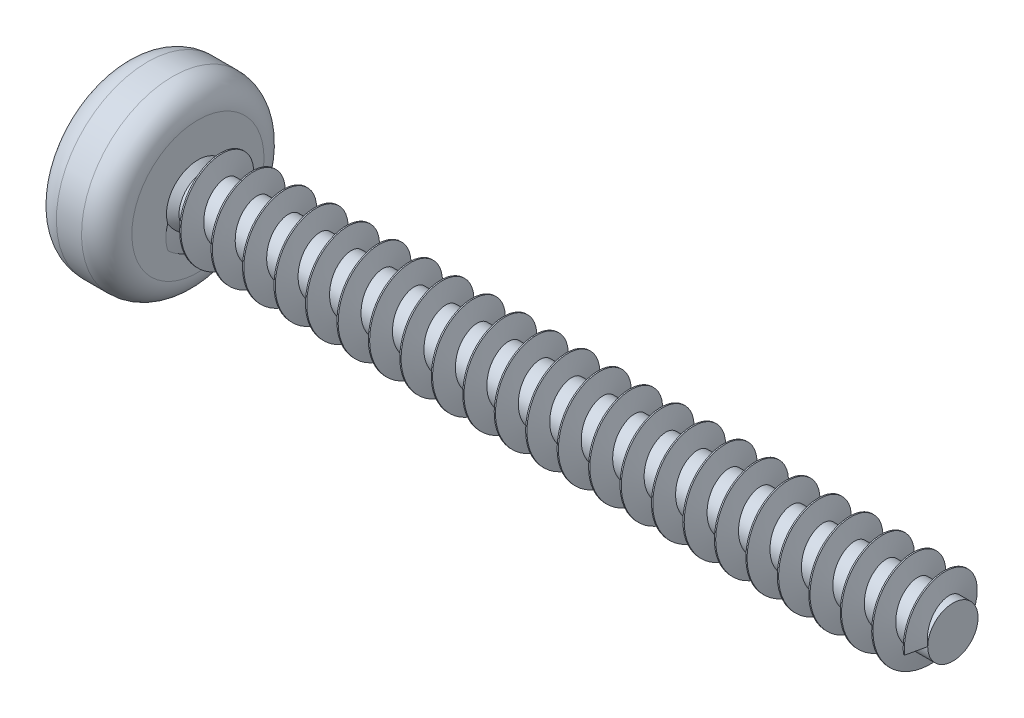
SolidWorks part; units mm, degrees
ref_plane "Front Plane" through (0, 0, 0) normal (0, 0, 1) x (1, 0, 0)
ref_plane "Top Plane" through (0, 0, 0) normal (0, 1, 0) x (1, 0, 0)
ref_plane "Right Plane" through (0, 0, 0) normal (1, 0, 0) x (0, 0, -1)
sketch "Sketch1" plane through (0, 0, 0) normal (0, 0, 1) x (1, 0, 0)
  line L0 (0, 0) -> (0, 1.05)
  line L1 (0.4, 1.45) -> (0.8, 1.45)
  line L2 (1.2, 1.05) -> (1.2, 0.5)
  line L3 (1.3, 0.4) -> (13.2, 0.4)
  line L4 (13.2, 0.4) -> (13.2, 0)
  line L5 (13.2, 0) -> (0, 0) construction
  line L6 (1.2, 0.5) -> (1.3, 0.4)
  line L7 (0, 0) -> (13.2, 0)
  arc A0 (0.8, 1.45) -> (1.2, 1.05) centre (0.8, 1.05) cw
  arc A1 (0, 1.05) -> (0.4, 1.45) centre (0.4, 1.05) cw
  point P5 (1.2, 0.4)
  point P9 (1.2, 1.45)
  point P12 (0, 1.45)
  dimension "D3" = 0.4
  dimension "D1" = 2.9
  dimension "D2" = 1.2
  dimension "D4" = 0.8
  dimension "ScrewLenght" = 12
revolve "Revolve1" add sketch "Sketch1" angle 360 about L5
sketch "Sketch2" plane through (0, 0, 0) normal (-1, 0, 0) x (0, 0, 1)
  line L1 (0.2, -0.85) -> (-0.2, -0.85)
  line L2 (0.2, -0.85) -> (0.2, 0.85)
  line L3 (0.2, 0.85) -> (-0.2, 0.85)
  line L4 (-0.2, -0.85) -> (-0.2, 0.85)
  line L5 (0.2, -0.85) -> (-0.2, 0.85) construction
  line L6 (0.2, 0.85) -> (-0.2, -0.85) construction
  line L7 (0.85, 0.2) -> (-0.85, 0.2)
  line L8 (0.85, 0.2) -> (0.85, -0.2)
  line L9 (0.85, -0.2) -> (-0.85, -0.2)
  line L10 (-0.85, 0.2) -> (-0.85, -0.2)
  line L11 (0.85, 0.2) -> (-0.85, -0.2) construction
  line L12 (0.85, -0.2) -> (-0.85, 0.2) construction
  point P0 (0, 0)
  point P6 (0, 0)
  dimension "D1" = 0.4
  dimension "D2" = 1.7
extrude "Cut-Extrude1" cut sketch "Sketch2" against normal blind 0.8 draft 9 contours L2 L9 L4 L1 | L7 L10 L9 L4 | L9 L2 L7 L4 | L7 L2 L3 L4 | L9 L8 L7 L2 region at (0, -0.525, 0) region at (0, 0, 0) region at (0, 0, 0.525) region at (0, 0, -0.525) region at (0, 0.525, 0)
thread "Thread3" pitch 0.3 method extrude profile "Thread Profile4" start angle 0, offset 0, length 0, pitch 0.5, diameter 0.8
ref_plane "Plane4" through (13.2, 0, 0.4) normal (0, -1, 0) x (0, 0, 1)
sketch "Thread Profile4" plane through (13.2, 0, 0.4) normal (0, -1, 0) x (0, 0, 1)
  line L0 (0, 0) -> (0, 0.3) construction
  line L1 (0, 0) -> (0.3, 0.0665)
  line L2 (0.3, 0.0665) -> (0.3, 0.0865)
  line L3 (0.3, 0.0865) -> (0, 0.153)
  line L4 (0.3, 0.0765) -> (0, 0.0765) construction
  line L11 (0, 0) -> (0, 0.153)
  point P2 (0, 0)
  dimension "Pitch" = 0.3
  dimension "Profile_Angle" = 25
  dimension "Profile_Land" = 0.02
  dimension "Profile_Height" = 0.3
